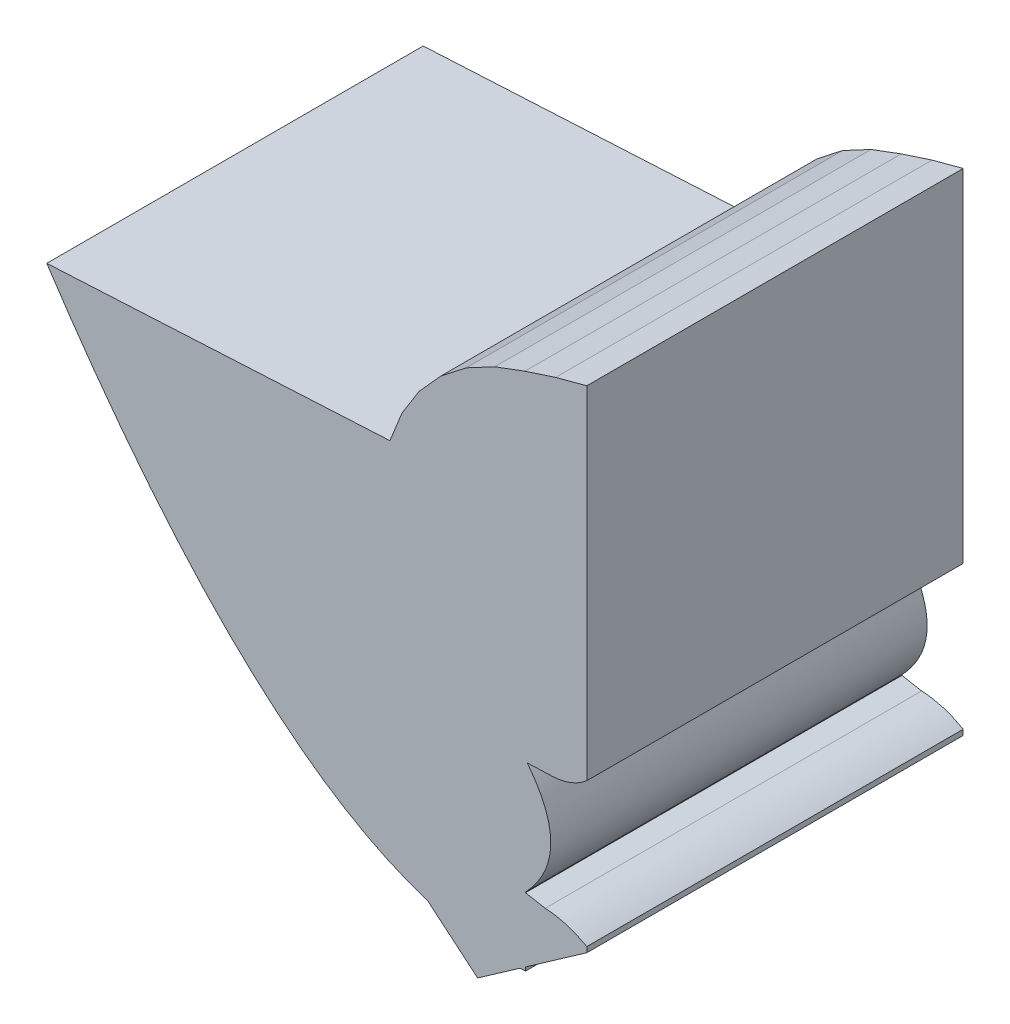
SolidWorks part; units mm, degrees
ref_plane "Alzado" through (0, 0, 0) normal (0, 0, 1) x (1, 0, 0)
ref_plane "Planta" through (0, 0, 0) normal (0, 1, 0) x (1, 0, 0)
ref_plane "Vista lateral" through (0, 0, 0) normal (1, 0, 0) x (0, 0, -1)
sketch "Croquis1" plane through (0, 0, 0) normal (0, 0, 1) x (1, 0, 0)
  line L0 (-8.9818, 12.6082) -> (-23.0359, 11.8716) construction
  line L1 (-8.9818, 12.6082) -> (-23.0359, 11.8716)
  line L2 (-8.9818, 12.6082) -> (-23.0359, 11.8716) construction
  line L3 (-2.1773, 6.1864) -> (-2.1773, -4.6845)
  line L4 (-8.9818, 12.6082) -> (-23.0359, 11.8716)
  line L6 (-1.3949, 1.9763) -> (0.3551, 2.2848) construction
  line L7 (-1.3949, 1.9763) -> (0.3551, 2.2848) construction
  line L8 (0.3551, 2.2848) -> (0.3551, 2.8423) construction
  line L9 (0.3551, 2.2848) -> (0.3551, 3.0015) construction
  line L10 (0.3551, -2.2848) -> (-1.3949, -2.2237) construction
  line L11 (0.3551, -2.2848) -> (-1.3949, -2.2237) construction
  line L12 (0.3551, 2.2848) -> (0.3551, -2.2848) construction
  line L13 (0.3551, -2.2848) -> (0.3551, -2.7233) construction
  line L14 (-8.9818, 12.6082) -> (-6.9949, 10.4774)
  line L15 (-23.0359, 11.5401) -> (-23.0359, 11.8716) construction
  line L16 (-23.0359, 11.5401) -> (-23.0359, 11.8716)
  arc A0 (-18.9452, 7.5409) -> (-23.0359, 11.5401) centre (-69.8841, -40.4718) ccw construction
  arc A1 (-18.9452, 7.5409) -> (-23.0359, 11.5401) centre (-69.8841, -40.4718) ccw
  spline S1 degree 2 poles (-4119.0151, 24659.0515) (3413.1083, -24757.661) (-2705.4818, 24835.5983) knots 0.405517 0.405517 0.405517 0.594449 0.594449 0.594449 weights 1 1 1 only from (-18.9452, 7.5409) to (-2.8466, -5.0591) construction
  spline S2 degree 2 poles (-18.9452, 7.5409) (-10.215, -3.6976) (-2.8466, -5.0591) knots 0.497667 0.497667 0.497667 0.499554 0.499554 0.499554 weights 1 1 1
  spline S3 degree 2 poles (-23607.9882, 8212.1168) (23492.4763, -8550.6979) (-23372.6553, 8887.1675) knots 0.40552 0.40552 0.40552 0.594498 0.594498 0.594498 weights 1 1 1 only from (0.3551, 3.0015) to (-6.9949, 10.4774) construction
  spline S4 degree 2 poles (-2.1773, 6.1864) (-4.0633, 8.1416) (-6.9949, 10.4774) knots 0.501383 0.501383 0.501383 0.502013 0.502013 0.502013 weights 1 1 1
  spline S5 degree 2 poles (-1.3949, -2.2237) (-0.9075, -0.1237) (-1.3949, 1.9763) knots 0 0 0 1 1 1 weights 1 3.231801 1 construction
  spline S6 degree 2 poles (-1.3949, -2.2237) (-0.9075, -0.1237) (-1.3949, 1.9763) knots 0 0 0 1 1 1 weights 1 3.231801 1 construction
  spline S7 degree 2 poles (-24934.0908, 1769.912) (24899.5391, -2178.5787) (-24858.838, 2586.1022) knots 0.405518 0.405518 0.405518 0.594474 0.594474 0.594474 weights 1 1 1 only from (-2.8466, -5.0591) to (0.3551, -2.7233) construction
  spline S8 degree 2 poles (-2.8466, -5.0591) (-2.4982, -4.873) (-2.1773, -4.6845) knots 0.498812 0.498812 0.498812 0.498912 0.498912 0.498912 weights 1 1 1
extrude "croquis base" add sketch "Croquis1" along normal mid plane 13.9874 contours S2 S8 L13 L11 S6 L7 L9 S4 L14 L1 L16 A1 region at (-10.1535, 5.1597, 0)
sketch "Croquis6" plane through (0, 0, 0) normal (1, 0, 0) x (0, 0, -1)
  line L0 (6.9937, 12.6082) -> (6.9937, 10.4774) construction
  line L1 (6.9937, 12.6082) -> (6.9937, -5.0591)
  line L2 (-6.9937, 12.6082) -> (-6.9937, 10.4774) construction
  line L3 (-6.9937, 12.6082) -> (-6.9937, -5.0591)
  line L4 (-6.9937, -5.0591) -> (6.9937, -5.0591) construction
  line L5 (-6.9937, -5.0591) -> (-4.9937, -5.0591)
  line L6 (6.9937, 12.6082) -> (4.9937, -5.0591)
  line L7 (-6.9937, 12.6082) -> (-4.9937, -5.0591)
  line L8 (4.9937, -5.0591) -> (6.9937, -5.0591)
  dimension "D1" = 2
  dimension "D2" = 2
sketch "Croquis9" plane through (0, 0, 0) normal (0, 0, 1) x (1, 0, 0)
  line L0 (0, 0) -> (-4.9559, 0) construction
  line L1 (-2.4454, 0.1046) -> (-1.25, 0) construction
  line L2 (-1.25, 0) -> (-1.25, -4.2203) construction
  line L3 (-2.1773, -1.8404) -> (-2.1773, -4.3883)
  line L4 (-2.1773, 6.1864) -> (-2.1773, -4.6845) construction
  line L5 (-2.4454, 0.1046) -> (-2.0532, -4.3783) construction
  line L6 (-2.4454, 0.1046) -> (-15.184, 3.0892) construction
  line L7 (-19.6099, 15.4015) -> (-15.184, 3.0892) construction
  line L9 (-15.184, 3.0892) -> (-25.9078, 12.6462) construction
  line L10 (-15.184, 3.0892) -> (-13.3572, 5.139) construction
  line L11 (-19.9694, 9.4938) -> (-10.3098, 10)
  line L12 (-10.3098, 10) -> (-2.1773, 6.0829)
  line L13 (-2.1773, 6.0829) -> (-2.1773, 2.4242)
  line L15 (-2.1773, 6.1864) -> (-2.1773, -4.6845) construction
  parabola Q0 (-2.1773, 2.4242) -> (-2.1773, -1.8404) focus (-2.4454, 0.1046) apex (-1.25, 0)
  parabola Q1 (-2.1773, -4.3883) -> (-19.9694, 9.4938) focus (-2.4454, 0.1046) apex (-2.0532, -4.3783)
  spline S0 degree 2 poles (-18.9452, 7.5409) (-10.215, -3.6976) (-2.8466, -5.0591) knots 0.497667 0.497667 0.497667 0.499554 0.499554 0.499554 weights 1 1 1 construction
  dimension "D1" = 95
  dimension "D2" = 1.25
  dimension "D3" = 1.2
  dimension "D4" = 4.5
  dimension "D5" = 5
  dimension "D6" = 3
  dimension "D7" = 10
extrude "lente ppal 1" add sketch "Croquis9" along normal up to surface and the other way up to surface contours Q1 L3 Q0 L13 L12 L11 region at (-9.1064, 3.5992, 0) up to face at (-11.7662, 6.8113, 6.9937) other way up to face at (-11.7662, 6.8113, -6.9937)
extrude "lente ppal 2" cut sketch "Croquis9<3>" against normal through all both and the other way through all flip side to cut
sketch "Croquis9<3>" plane through (0, 0, 0) normal (0, 0, 1) x (1, 0, 0) same geometry as "Croquis9"
sketch "Croquis8" plane through (0, 0, 0) normal (0, 0, 1) x (1, 0, 0)
  line L0 (-8.9818, 12.6082) -> (-23.0359, 11.8716) construction
  line L1 (-10.3098, 10) -> (0.1, 15.5879) construction
  line L3 (0.1, 2.8777) -> (0.1, 15.5879)
  line L5 (-7.2179, 10.162) -> (-6.7684, 11.2747)
  line L6 (-6.7684, 11.2747) -> (-6.1325, 12.2923)
  line L7 (-6.1325, 12.2923) -> (-5.3295, 13.1841)
  line L8 (-5.3295, 13.1841) -> (-4.3839, 13.9229)
  line L9 (-4.3839, 13.9229) -> (-3.3244, 14.4863)
  line L10 (-3.3244, 14.4863) -> (-2.2004, 14.9065)
  line L11 (-2.2004, 14.9065) -> (-1.0591, 15.2773)
  line L12 (-1.0591, 15.2773) -> (0.1, 15.5879)
  line L13 (-0.5, 2) -> (-9.2621, 13.0152) construction
  line L14 (-9.2621, 13.0152) -> (-9.6721, 13.4466) construction
  line L15 (-9.2621, 13.0152) -> (-9.8313, 13.8617) construction
  line L16 (-0.5, 2) -> (-6.9932, 10.7183) construction
  line L17 (-6.9932, 10.7183) -> (-9.8657, 11.8789) construction
  line L18 (-0.5, 2) -> (-6.4504, 11.7835) construction
  line L19 (-1.1905, 2.3769) -> (-13.6677, 1.9412) construction
  line L20 (-6.4504, 11.7835) -> (-8.5297, 13.0828) construction
  line L21 (-0.5, 2) -> (-5.731, 12.7382) construction
  line L22 (-0.5, 2) -> (-4.8567, 13.5535) construction
  line L23 (-4.8567, 13.5535) -> (-7.2264, 16.5865) construction
  line L24 (-0.5, 2) -> (-3.8542, 14.2046) construction
  line L25 (-3.8542, 14.2046) -> (-5.6175, 17.521) construction
  line L26 (-0.5, 2) -> (-2.7624, 14.6964) construction
  line L27 (-2.7624, 14.6964) -> (-4.1395, 18.3795) construction
  line L28 (-0.5, 2) -> (-1.6297, 15.0919) construction
  line L29 (-1.6297, 15.0919) -> (-2.365, 17.3548) construction
  line L30 (-0.5, 2) -> (-0.4796, 15.4326) construction
  line L31 (-0.4796, 15.4326) -> (-1.0837, 17.6873) construction
  line L32 (-6.4504, 11.7835) -> (-9.194, 13.4978) construction
  line L33 (-5.731, 12.7382) -> (-8.3325, 15.0806) construction
  line L34 (-10.3098, 10) -> (-10.3098, 19.2428) construction
  line L35 (-0.4796, 15.4326) -> (-1.3923, 18.839) construction
  line L36 (-10.3098, 10) -> (-7.2179, 10.162)
  line L37 (-6.9932, 10.7183) -> (-7.7178, 13.8573) construction
  line L38 (-6.9932, 10.7183) -> (-7.6851, 10.9979) construction
  line L39 (-6.4504, 11.7835) -> (-7.328, 15.5847) construction
  line L40 (-6.4504, 11.7835) -> (-8.1247, 12.8297) construction
  line L41 (-5.731, 12.7382) -> (-6.4786, 15.9764) construction
  line L42 (-5.731, 12.7382) -> (-7.1919, 14.0536) construction
  line L43 (-4.8567, 13.5535) -> (-5.8037, 17.6554) construction
  line L44 (-4.8567, 13.5535) -> (-6.0786, 15.1174) construction
  line L45 (-3.8542, 14.2046) -> (-4.8235, 18.4032) construction
  line L46 (-3.8542, 14.2046) -> (-4.9673, 16.2982) construction
  line L47 (-2.7624, 14.6964) -> (-3.6965, 18.7423) construction
  line L48 (-2.7624, 14.6964) -> (-3.4418, 16.5134) construction
  line L49 (-0.5, 2) -> (-0.5437, 2.5) construction
  line L50 (-0.5437, 2.5) -> (-0.8858, 3.4397) construction
  line L51 (0, 0) -> (0, 1.5958) construction
  line L52 (0, 12.6082) -> (0, -5.0591) construction
  line L53 (-1.6297, 15.0919) -> (-2.8173, 18.7468) construction
  line L54 (-1.6297, 15.0919) -> (-2.2911, 17.9567) construction
  line L55 (-0.4796, 15.4326) -> (-1.0428, 17.8722) construction
  line L56 (-10.3098, 10) -> (-2.1773, 2.3425)
  line L57 (-2.1773, 2.3425) -> (-1.1905, 2.3769)
  line L58 (-10.3098, 10) -> (-19.9694, 9.4938) construction
  line L60 (-2.1773, 6.0829) -> (-10.3098, 10) construction
  parabola Q0 (-1.1905, 2.3769) -> (0.1, 2.8777) focus (-0.8858, 3.4397) apex (-0.5437, 2.5)
  spline S1 degree 2 poles (-10.3098, 10) (-2.4445, 4.1882) (-0.2283, 0.4324) knots 0.500548 0.500548 0.500548 0.502013 0.502013 0.502013 weights 1 1 1 construction
  dimension "D1" = 5.039
  dimension "D3" = 15
  dimension "D4" = 25
  dimension "D5" = 80
  dimension "D6" = 45
  dimension "D7" = 35
  dimension "D8" = 7.5
  dimension "D9" = 5
  dimension "D10" = 55
  dimension "D11" = 211.322
  dimension "D12" = 206.691
  dimension "D13" = 202.027
  dimension "D14" = 197.339
  dimension "D15" = 192.633
  dimension "D16" = 0.5
  dimension "D17" = 0.5
  dimension "D18" = 2
  dimension "D19" = 5
  dimension "D20" = 20
  dimension "D21" = 88
  dimension "D22" = 1
  dimension "D23" = 0.1
  dimension "D24" = 178
  dimension "D25" = 1.2
  dimension "D26" = 10
extrude "lente frontal" add sketch "Croquis8" along normal up to surface and the other way up to surface up to face at (-5.0154, 2.8272, 6.9937) other way up to face at (-7.9808, 4.4301, -6.9937)
sketch "Croquis11" plane through (0, 0, 0) normal (0, 0, 1) x (1, 0, 0)
  line L0 (0, 0) -> (0, -3.4622) construction
  line L1 (0, 0) -> (3.4097, 0) construction
  line L2 (0, 0) -> (-1.5, -2) construction
  line L3 (0.0193, -2.4148) -> (0.0108, -2.901) construction
  line L4 (-1.5262, -3.4998) -> (-1.5, -2) construction
  line L5 (-1.4477, -2.0014) -> (-2.6004, -1.9611) construction
  line L6 (0.0108, -2.901) -> (-0.0904, -2.7858) construction
  line L7 (0.1, -2.4588) -> (0.1, -2.6588)
  line L8 (0.1, 2.8777) -> (0.1, 15.5879) construction
  line L9 (0.0108, -2.901) -> (0.8474, -2.1663) construction
  line L10 (-0.4724, -2.8467) -> (0.0108, -2.901) construction
  line L11 (-1.3889, -2.3589) -> (-0.0204, -2.973) construction
  line L12 (-0.0204, -2.973) -> (-2.5614, -3.2818) construction
  line L13 (-0.0204, -2.973) -> (-1.479, -0.8696) construction
  line L14 (-1.4477, -2.0014) -> (-10.0297, -0.405)
  line L15 (-10.0297, -0.405) -> (-3.9576, -5.5)
  line L16 (-3.9576, -5.5) -> (-3.9576, 4.2291) construction
  line L17 (0.1, -2.6588) -> (-3.9576, -5.5)
  parabola Q0 (-1.4477, -2.0014) -> (0.1, -2.4588) focus (-1.5262, -3.4998) apex (-1.5, -2)
  parabola Q1 (0.1, -2.6588) -> (-3.9576, -5.5) focus (-1.3889, -2.3589) apex (-0.0204, -2.973) construction
  dimension "D1" = 2
  dimension "D2" = 88
  dimension "D3" = 1.5
  dimension "D4" = 1.5
  dimension "D5" = 1
  dimension "D6" = 0.2
  dimension "D7" = 5.5
  dimension "D8" = 1.5
  dimension "D9" = 105
  dimension "D10" = 55
extrude "lente trasera" add sketch "Croquis11" along normal up to surface and the other way up to surface up to face at (-3.7041, 8.4573, 6.9937) other way up to face at (-4.8085, 9.1371, -6.9937)
